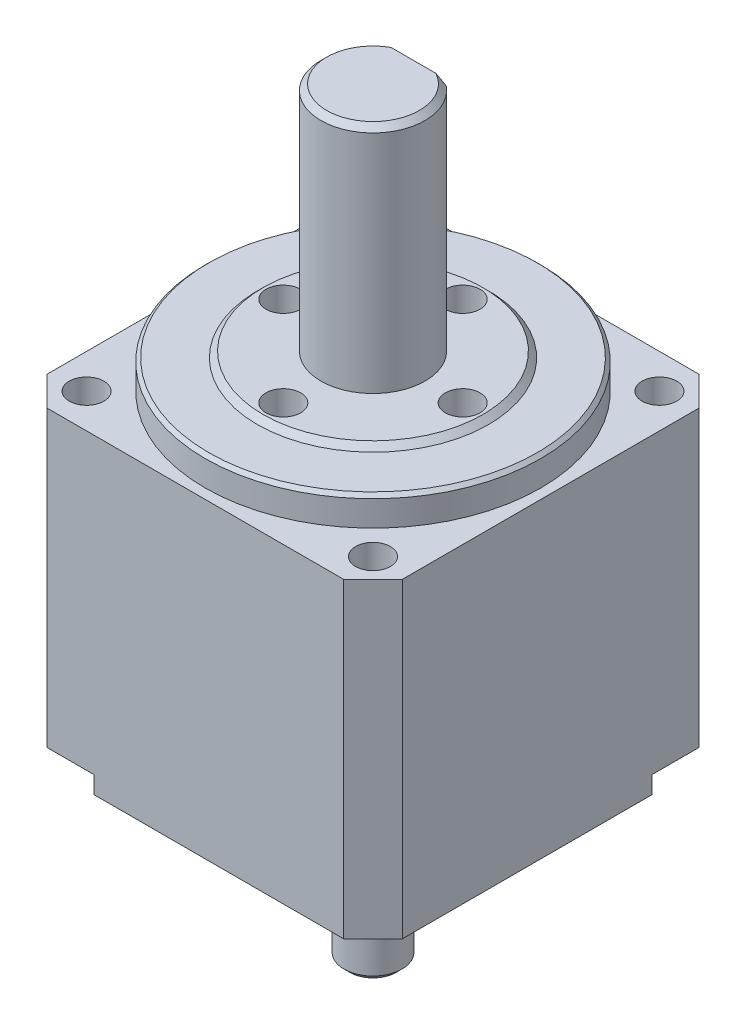
SolidWorks part; units mm, degrees
ref_plane "前视基准面" through (0, 0, 0) normal (0, 0, 1) x (1, 0, 0)
ref_plane "上视基准面" through (0, 0, 0) normal (0, 1, 0) x (1, 0, 0)
ref_plane "右视基准面" through (0, 0, 0) normal (1, 0, 0) x (0, 0, -1)
other "Configuration Table"
sketch "草图1" plane through (0, 0, 0) normal (0, 1, 0) x (1, 0, 0)
  line L1 (15.35, -15.35) -> (-15.35, -15.35)
  line L2 (15.35, -15.35) -> (15.35, 15.35)
  line L3 (15.35, 15.35) -> (-15.35, 15.35)
  line L4 (-15.35, -15.35) -> (-15.35, 15.35)
  line L5 (15.35, -15.35) -> (-15.35, 15.35) construction
  line L6 (15.35, 15.35) -> (-15.35, -15.35) construction
  point P0 (0, 0)
  dimension "D1" = 30.7
  dimension "D2" = 30.7
extrude "凸台-拉伸1" add sketch "草图1" along normal blind 26.9
sketch "草图2" plane through (0, 26.9, 0) normal (0, 1, 0) x (1, 0, 0)
  circle A0 centre (0, 0) radius 14.5
  dimension "D1" = 29
extrude "凸台-拉伸2" add sketch "草图2" along normal blind 2.5
sketch "草图3" plane through (0, 29.4, 0) normal (0, 1, 0) x (1, 0, 0)
  circle A0 centre (0, 0) radius 9.5
  dimension "D1" = 19
extrude "凸台-拉伸3" add sketch "草图3" along normal blind 0.5
chamfer "倒角1" distance 0.5 angle 45 1 edges at (0, 29.4, 9.5)
chamfer "倒角2" distance 0.3 angle 45 1 edges at (0, 29.4, 14.5)
sketch "草图4" plane through (0, 29.9, 0) normal (0, 1, 0) x (1, 0, 0)
  circle A0 centre (0, 0) radius 4.5
  dimension "D1" = 9
extrude "凸台-拉伸4" add sketch "草图4" along normal blind 20
sketch "草图5" plane through (0, 0, 0) normal (0, -1, 0) x (1, 0, 0)
  circle A0 centre (0, 0) radius 8
  dimension "D1" = 16
extrude "凸台-拉伸5" add sketch "草图5" along normal blind 2.6
sketch "草图6" plane through (0, -2.6, 0) normal (0, -1, 0) x (1, 0, 0)
  circle A0 centre (0, 0) radius 2.5
  dimension "D1" = 5
extrude "凸台-拉伸6" add sketch "草图6" along normal blind 13
chamfer "倒角3" distance 0.5 angle 45 2 edges at (0, -2.6, -8) (0, -15.6, -2.5)
sketch "草图7" plane through (0, 0, 0) normal (0, -1, 0) x (1, 0, 0)
  line L0 (-15.35, 8.75) -> (-12, 8.75)
  line L1 (-15.35, -15.35) -> (-15.35, 15.35) construction
  line L2 (-8.75, 12) -> (-8.75, 15.35)
  line L3 (-15.35, 15.35) -> (15.35, 15.35) construction
  line L4 (-8.75, 15.35) -> (-15.35, 15.35)
  line L5 (-15.35, 15.35) -> (-15.35, 8.75)
  line L6 (15.35, -15.35) -> (15.35, -8.75)
  line L7 (15.35, 15.35) -> (15.35, -15.35) construction
  line L8 (15.35, -8.75) -> (12, -8.75)
  line L9 (8.75, -12) -> (8.75, -15.35)
  line L10 (15.35, -15.35) -> (-15.35, -15.35) construction
  line L11 (8.75, -15.35) -> (15.35, -15.35)
  arc A0 (-12, 8.75) -> (-8.75, 12) centre (-12, 12) ccw
  arc A1 (12, -8.75) -> (8.75, -12) centre (12, -12) ccw
  dimension "D3" = 3.25
  dimension "D6" = 3.25
  dimension "D1" = 6.6
  dimension "D2" = 6.6
  dimension "D4" = 6.6
  dimension "D5" = 6.6
extrude "切除-拉伸1" cut sketch "草图7" against normal blind 1.5
sketch "草图8" plane through (0, 26.9, 0) normal (0, 1, 0) x (1, 0, 0)
  line L1 (12.3744, -12.3744) -> (-12.3744, -12.3744) construction
  line L2 (12.3744, -12.3744) -> (12.3744, 12.3744) construction
  line L3 (12.3744, 12.3744) -> (-12.3744, 12.3744) construction
  line L4 (-12.3744, -12.3744) -> (-12.3744, 12.3744) construction
  line L5 (12.3744, -12.3744) -> (-12.3744, 12.3744) construction
  line L6 (12.3744, 12.3744) -> (-12.3744, -12.3744) construction
  circle A0 centre (0, 0) radius 17.5 construction
  circle A1 centre (-12.3744, 12.3744) radius 1.5
  circle A2 centre (12.3744, 12.3744) radius 1.5
  circle A3 centre (12.3744, -12.3744) radius 1.5
  circle A4 centre (-12.3744, -12.3744) radius 1.5
  dimension "D1" = 35
  dimension "D2" = 3
extrude "切除-拉伸2" cut sketch "草图8" against normal blind 6
sketch "草图9" plane through (0, 20.9, 0) normal (0, 1, 0) x (1, 0, 0)
  circle A0 centre (12.3744, -12.3744) radius 1.25
  circle A1 centre (12.3744, 12.3744) radius 1.25
  circle A2 centre (-12.3744, 12.3744) radius 1.25
  circle A3 centre (-12.3744, -12.3744) radius 1.25
  dimension "D1" = 2.5
extrude "切除-拉伸3" cut sketch "草图9" against normal blind 1.5
sketch "草图10" plane through (0, 29.9, 0) normal (0, 1, 0) x (1, 0, 0)
  line L0 (0, 0) -> (-12.0728, 0) construction
  circle A0 centre (-7.75, 0) radius 1.5
  circle A1 centre (0, 7.75) radius 1.5
  circle A2 centre (7.75, 0) radius 1.5
  circle A3 centre (0, -7.75) radius 1.5
  point P14 (0, 0)
  dimension "D1" = 3
  dimension "D2" = 7.75
  dimension "D3" = 4
extrude "切除-拉伸4" cut sketch "草图10" against normal blind 4
sketch "草图11" plane through (0, 25.9, 0) normal (0, 1, 0) x (1, 0, 0)
  circle A0 centre (0, 7.75) radius 1.25
  circle A1 centre (-7.75, 0) radius 1.25
  circle A2 centre (7.75, 0) radius 1.25
  circle A3 centre (0, -7.75) radius 1.25
  dimension "D1" = 2.5
extrude "切除-拉伸5" cut sketch "草图11" against normal blind 1.5
chamfer "倒角4" distance 2.529 angle 45 4 edges at (15.35, 14.2, -15.35) (-15.35, 13.45, -15.35) (-15.35, 14.2, 15.35) (15.35, 13.45, 15.35)
chamfer "倒角5" distance 0.5 angle 45 1 edges at (0, 49.9, 4.5)
sketch "草图12" plane through (0, 49.9, 0) normal (0, 1, 0) x (1, 0, 0)
  line L0 (-2.8284, 3.5) -> (2.8284, 3.5)
  circle A0 centre (0, 0) radius 4.5 construction
  arc A1 (2.8284, 3.5) -> (-2.8284, 3.5) centre (0, 0) ccw
  dimension "D1" = 3.5
extrude "切除-拉伸6" cut sketch "草图12" against normal blind 18
sketch "草图13" plane through (0, -15.6, 0) normal (0, -1, 0) x (1, 0, 0)
  line L0 (-1.5, -2) -> (1.5, -2)
  circle A0 centre (0, 0) radius 2.5 construction
  arc A1 (-1.5, -2) -> (1.5, -2) centre (0, 0) ccw
  dimension "D1" = 2
extrude "切除-拉伸7" cut sketch "草图13" against normal blind 11
